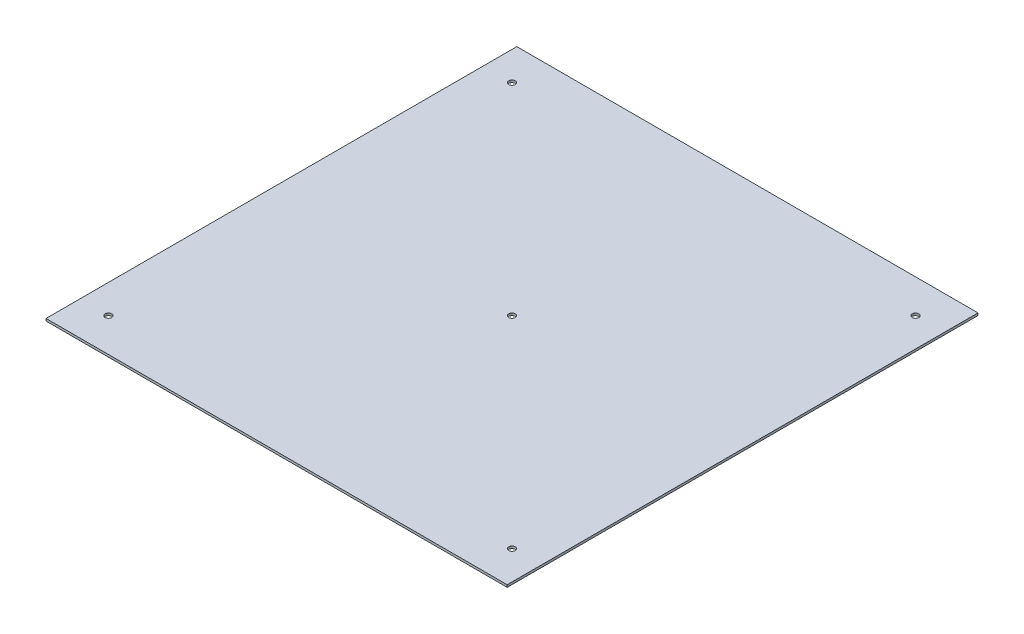
SolidWorks part; units mm, degrees
ref_plane "Front" through (0, 0, 0) normal (0, 0, 1) x (1, 0, 0)
ref_plane "Top" through (0, 0, 0) normal (0, 1, 0) x (1, 0, 0)
ref_plane "Right" through (0, 0, 0) normal (1, 0, 0) x (0, 0, -1)
sketch "Sketch1" plane through (0, 0, 0) normal (0, 1, 0) x (1, 0, 0)
  line L1 (120, 122.5) -> (-120, 122.5)
  line L2 (120, 122.5) -> (120, -122.5)
  line L3 (120, -122.5) -> (-120, -122.5)
  line L4 (-120, 122.5) -> (-120, -122.5)
  line L5 (0, -122.5) -> (0, 122.5) construction
  line L6 (120, 0) -> (-120, 0) construction
  point P0 (0, 0)
  dimension "D1" = 245
  dimension "D2" = 240
extrude "Boss-Extrude1" add sketch "Sketch1" along normal blind 1.2
hole_wizard "M3 Clearance Hole1" positions "Sketch2" profile "Sketch3" hole size "M3" standard "ANSI Metric" end condition through all
sketch "Sketch2" plane through (0, 1.2, 0) normal (0, 1, 0) x (1, 0, 0)
  line L1 (-105, -105) -> (105, -105)
  line L2 (-105, -105) -> (-105, 105)
  line L3 (-105, 105) -> (105, 105)
  line L4 (105, -105) -> (105, 105)
  line L5 (0, 105) -> (0, -105) construction
  line L6 (-105, 0) -> (105, 0) construction
  point P1 (0, 0)
  point P2 (105, 105)
  point P273 (-105, -105)
  point P274 (-105, 105)
  point P275 (105, -105)
  dimension "D1" = 210
sketch "Sketch3" plane through (0, 1.2, 0) normal (1, 0, 0) x (0, 0, 1)
  line L0 (0, 0) -> (0, 1.2)
  line L1 (0, 1.2) -> (1.7, 1.2)
  line L2 (1.7, 1.2) -> (1.7, 0)
  line L5 (1.7, 0) -> (0, 0)
  line L11 (0, -6.35) -> (0, 107.95) construction
  dimension "Thru Hole Dia." = 3.4
  dimension "Thru Hole Depth" = 1.2
